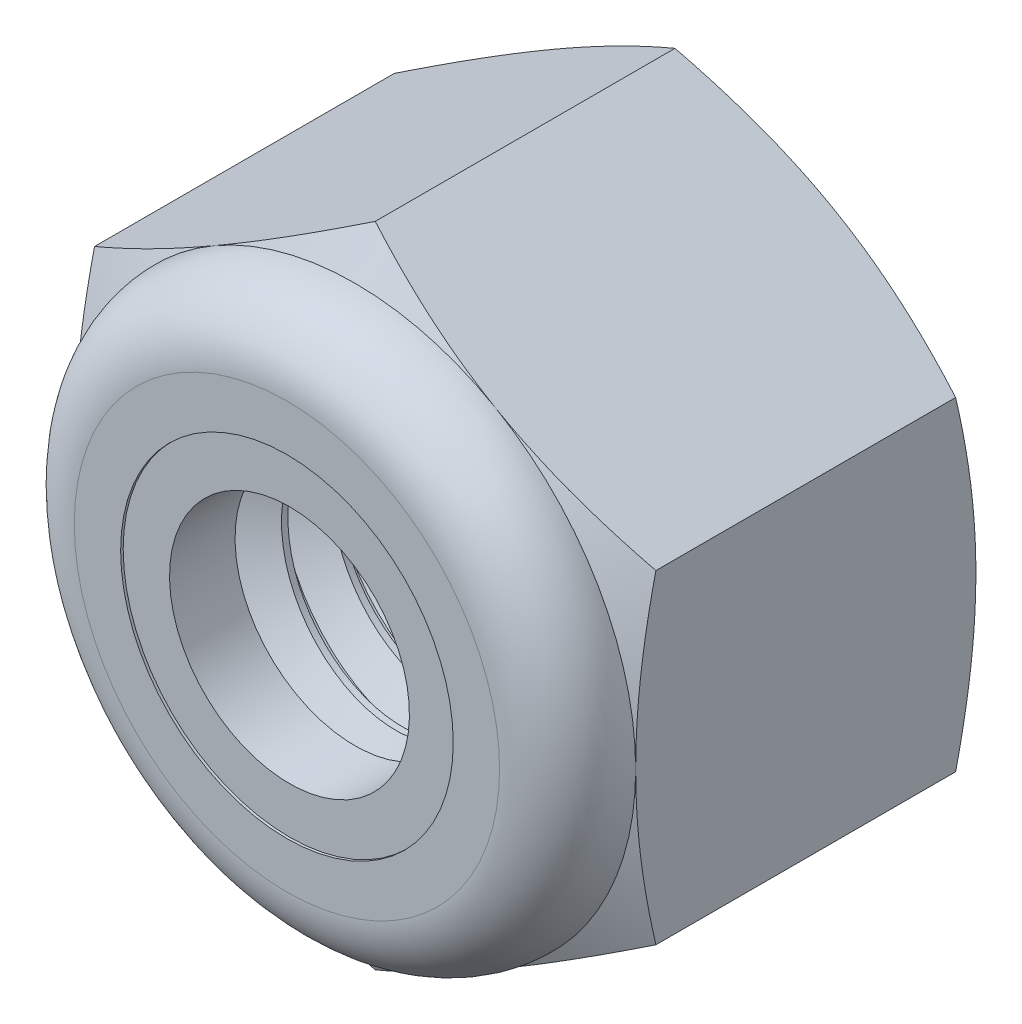
SolidWorks part; units mm, degrees
material "Plain Carbon Steel"
ref_plane "Front Plane" through (0, 0, 0) normal (0, 0, 1) x (1, 0, 0)
ref_plane "Top Plane" through (0, 0, 0) normal (0, 1, 0) x (1, 0, 0)
ref_plane "Right Plane" through (0, 0, 0) normal (1, 0, 0) x (0, 0, -1)
sketch "Sketch1" plane through (0, 0, 0) normal (0, 0, 1) x (1, 0, 0)
  line L1 (0, 3.1754) -> (-2.75, 1.5877)
  line L2 (-2.75, 1.5877) -> (-2.75, -1.5877)
  line L3 (-2.75, -1.5877) -> (0, -3.1754)
  line L4 (0, -3.1754) -> (2.75, -1.5877)
  line L5 (2.75, -1.5877) -> (2.75, 1.5877)
  line L6 (2.75, 1.5877) -> (0, 3.1754)
  circle A0 centre (0, 0) radius 2.75 construction
  circle A1 centre (0, 0) radius 1.5
  point P10 (0, -1.5)
  point P11 (0, 1.5)
  point P12 (0, 2.75)
  dimension "Thread Size" = 3
  dimension "Width" = 5.5
sketch "Sketch2" plane through (0, 0, 0) normal (1, 0, 0) x (0, 0, -1)
  line L0 (2, 0) -> (-2, 0) construction
  line L1 (-2, 1.5) -> (2, 1.5) construction
  line L2 (-1.975, -1.6293) -> (-3.27, -1.6293) construction
  line L3 (-2.4688, 1.5541) -> (-1.9688, 1.5541) construction
  line L4 (-1.9688, 1.5541) -> (-2.2188, 1.1211) construction
  line L5 (-2.2188, 1.1211) -> (-2.4688, 1.5541) construction
  line L6 (-2.4375, 1.5) -> (-2, 1.5) construction
  line L7 (-2.25, 1.1752) -> (-2.1875, 1.1752) construction
  line L8 (-2.2188, 1.1752) -> (-2.2188, 1.1211) construction
  line L9 (-2.2188, 1.5) -> (-2.2188, 1.5541) construction
  line L10 (-1.9844, 1.5271) -> (-2.4531, 1.5271)
  line L11 (-2.4531, 1.5271) -> (-2.25, 1.1752)
  line L12 (-2.25, 1.1752) -> (-2.1875, 1.1752)
  line L13 (-2.1875, 1.1752) -> (-1.9844, 1.5271)
  line L14 (2, 0) -> (3.27, 0)
  line L15 (3.27, 0) -> (3.27, 4.4454)
  line L16 (0, 4.4454) -> (0, 3.1754) construction
  line L17 (0, 3.1754) -> (0, 1.5877) construction
  line L18 (2, 2.75) -> (-1.3333, 2.75) construction
  line L19 (-2.25, -1.1752) -> (-2.1875, -1.1752) construction
  line L20 (2, 2.75) -> (2, 0)
  line L21 (1.8016, 3.1754) -> (-1.135, 3.1754)
  line L22 (2, 2.75) -> (1.8016, 3.1754)
  line L23 (-2, 0) -> (-2, 2.0833) construction
  line L24 (-1.3333, 2.75) -> (-1.135, 3.1754)
  line L25 (3.27, 4.4454) -> (-3.27, 4.4454)
  line L26 (-2, 2.0833) -> (-3.27, 2.0833)
  line L27 (-3.27, 2.0833) -> (-3.27, 4.4454)
  line L28 (-1.975, 2.0833) -> (-1.975, 1.1752) construction
  line L29 (-1.975, 1.6293) -> (-3.27, 1.6293)
  line L30 (-3.27, 1.6293) -> (-3.27, 0)
  line L31 (-3.27, 0) -> (-1.3333, 0)
  line L32 (-1.3333, 0) -> (-1.3333, 2.725)
  line L33 (-1.975, 1.6293) -> (-1.975, 2.0833)
  arc A0 (-1.3333, 2.75) -> (-2, 2.0833) centre (-1.3333, 2.0833) ccw
  arc A1 (-1.3333, 2.725) -> (-1.975, 2.0833) centre (-1.3333, 2.0833) ccw
  point P4 (0, 0)
  point P18 (-2.2188, 1.5271)
  point P22 (-2.2188, 1.5271)
  point P33 (0, 3.1754)
  point P48 (-3.27, -1.6293)
  point P51 (-2.25, -1.1752)
  dimension "Height" = 4
  dimension "Pitch" = 0.5
  dimension "D1" = 0.0625
  dimension "D2" = 1.27
  dimension "D3" = 25
  dimension "D4" = 0.6667
  dimension "D5" = 25
  dimension "D6" = 0.025
sketch "Sketch3" plane through (0, 0, 0) normal (0, 0, 1) x (1, 0, 0)
  line L0 (0, -3.1754) -> (2.75, -1.5877) construction
  line L1 (2.75, -1.5877) -> (2.75, 1.5877) construction
  line L2 (2.75, 1.5877) -> (0, 3.1754) construction
  line L3 (0, 3.1754) -> (-2.75, 1.5877) construction
  line L4 (-2.75, 1.5877) -> (-2.75, -1.5877) construction
  line L5 (-2.75, -1.5877) -> (0, -3.1754) construction
  line L6 (0, -3.1754) -> (2.75, -1.5877)
  line L7 (2.75, -1.5877) -> (2.75, 1.5877)
  line L8 (2.75, 1.5877) -> (0, 3.1754)
  line L9 (0, 3.1754) -> (-2.75, 1.5877)
  line L10 (-2.75, 1.5877) -> (-2.75, -1.5877)
  line L11 (-2.75, -1.5877) -> (0, -3.1754)
  circle A0 centre (0, 0) radius 1.5 construction
  circle A1 centre (0, 0) radius 1.5
extrude "Boss-Extrude1" add sketch "Sketch3" along normal mid plane 4
sketch "Sketch4" plane through (0, 0, 0) normal (1, 0, 0) x (0, 0, -1)
  line L0 (3.27, 4.4454) -> (-3.27, 4.4454) construction
  line L1 (-3.27, 2.0833) -> (-3.27, 4.4454) construction
  line L2 (-2, 2.0833) -> (-3.27, 2.0833) construction
  line L3 (-1.3333, 2.75) -> (-1.135, 3.1754) construction
  line L4 (1.8016, 3.1754) -> (-1.135, 3.1754) construction
  line L5 (2, 2.75) -> (1.8016, 3.1754) construction
  line L6 (2, 2.75) -> (2, 0) construction
  line L7 (2, 0) -> (3.27, 0) construction
  line L8 (3.27, 0) -> (3.27, 4.4454) construction
  line L9 (-3.27, 1.6293) -> (-3.27, 0) construction
  line L10 (-3.27, 0) -> (-1.3333, 0) construction
  line L11 (-1.3333, 0) -> (-1.3333, 2.725) construction
  line L12 (-1.975, 1.6293) -> (-1.975, 2.0833) construction
  line L13 (-1.975, 1.6293) -> (-3.27, 1.6293) construction
  line L14 (3.27, 4.4454) -> (-3.27, 4.4454)
  line L15 (-3.27, 2.0833) -> (-3.27, 4.4454)
  line L16 (-2, 2.0833) -> (-3.27, 2.0833)
  line L17 (-1.3333, 2.75) -> (-1.135, 3.1754)
  line L18 (1.8016, 3.1754) -> (-1.135, 3.1754)
  line L19 (2, 2.75) -> (1.8016, 3.1754)
  line L20 (2, 2.75) -> (2, 0)
  line L21 (2, 0) -> (3.27, 0)
  line L22 (3.27, 0) -> (3.27, 4.4454)
  line L23 (-3.27, 1.6293) -> (-3.27, 0)
  line L24 (-3.27, 0) -> (-1.3333, 0)
  line L25 (-1.3333, 0) -> (-1.3333, 2.725)
  line L26 (-1.975, 1.6293) -> (-1.975, 2.0833)
  line L27 (-1.975, 1.6293) -> (-3.27, 1.6293)
  arc A0 (-1.3333, 2.75) -> (-2, 2.0833) centre (-1.3333, 2.0833) ccw construction
  arc A1 (-1.3333, 2.725) -> (-1.975, 2.0833) centre (-1.3333, 2.0833) ccw construction
  arc A2 (-1.3333, 2.75) -> (-2, 2.0833) centre (-1.3333, 2.0833) ccw
  arc A3 (-1.3333, 2.725) -> (-1.975, 2.0833) centre (-1.3333, 2.0833) ccw
revolve "Cut-Revolve1" cut sketch "Sketch4" angle 360 about L0
sketch "Sketch5" plane through (0, 0, 0) normal (1, 0, 0) x (0, 0, -1)
  line L0 (-1.975, 2.0833) -> (-1.975, 1.1752) construction
  line L1 (-1.3333, 0) -> (-1.3333, 2.725) construction
  line L2 (-1.975, 2.0833) -> (-1.975, 1.1752)
  line L3 (-1.3333, 1.1752) -> (-1.3333, 2.725)
  line L4 (-1.975, 1.1752) -> (-1.3333, 1.1752)
  arc A0 (-1.3333, 2.725) -> (-1.975, 2.0833) centre (-1.3333, 2.0833) ccw construction
  arc A1 (-1.3333, 2.725) -> (-1.975, 2.0833) centre (-1.3333, 2.0833) ccw
revolve "Revolve1" add sketch "Sketch5" angle 360 about L0
sketch "Sketch6" plane through (0, 0, 2) normal (0, 0, 1) x (1, 0, 0)
  circle A0 centre (0, 0) radius 1.5 construction
  circle A1 centre (0, 0) radius 1.5
curve "Helix/Spiral1" pitch 0.5 height 4.5 radius 1.5 centre (0, 0, 2) axis (0, 0, -1) start towards (0, 1, 0)
sketch "Sketch7" plane through (0, 0, 0) normal (1, 0, 0) x (0, 0, -1)
  line L0 (-2.4531, 1.5271) -> (-2.25, 1.1752) construction
  line L1 (-2.25, 1.1752) -> (-2.1875, 1.1752) construction
  line L2 (-2.1875, 1.1752) -> (-1.9844, 1.5271) construction
  line L3 (-1.9844, 1.5271) -> (-2.4531, 1.5271) construction
  line L4 (-2.4531, 1.5271) -> (-2.25, 1.1752)
  line L5 (-2.25, 1.1752) -> (-2.1875, 1.1752)
  line L6 (-2.1875, 1.1752) -> (-1.9844, 1.5271)
  line L7 (-1.9844, 1.5271) -> (-2.4531, 1.5271)
sweep "Sweep1" add profiles "Sketch7" path "Helix/Spiral1"
sketch "Sketch8" plane through (0, 0, -2) normal (0, 0, -1) x (-1, 0, 0)
  circle A2 centre (0, 0) radius 1.5271
  point P2 (0, 1.5271)
extrude "Cut-Extrude1" cut sketch "Sketch8" along normal through all and the other way through all draft 60
sketch "Sketch9" plane through (0, 0, 1.3333) normal (0, 0, 1) x (1, 0, 0)
  circle A2 centre (0, 0) radius 1.5271
  circle A3 centre (0, 0) radius 1.1752 construction
  point P2 (0, 1.5271)
  point P4 (0, 1.1752)
extrude "Cut-Extrude2" cut sketch "Sketch9" along normal through all and the other way through all draft 60
equation "\"D1@Sketch2\" = \"Pitch@Sketch2\" / 8"
equation "\"D4@Sketch2\"=\"Height@Sketch2\"/6"
equation "\"D1@Boss-Extrude1\"=\"Height@Sketch2\""
equation "\"D3@Helix/Spiral1\"=\"Height@Sketch2\"+\"Pitch@Sketch2\""
equation "\"D4@Helix/Spiral1\"=\"Pitch@Sketch2\""
equation "\"D6@Sketch2\"=\"Pitch@Sketch2\"*0.05"
